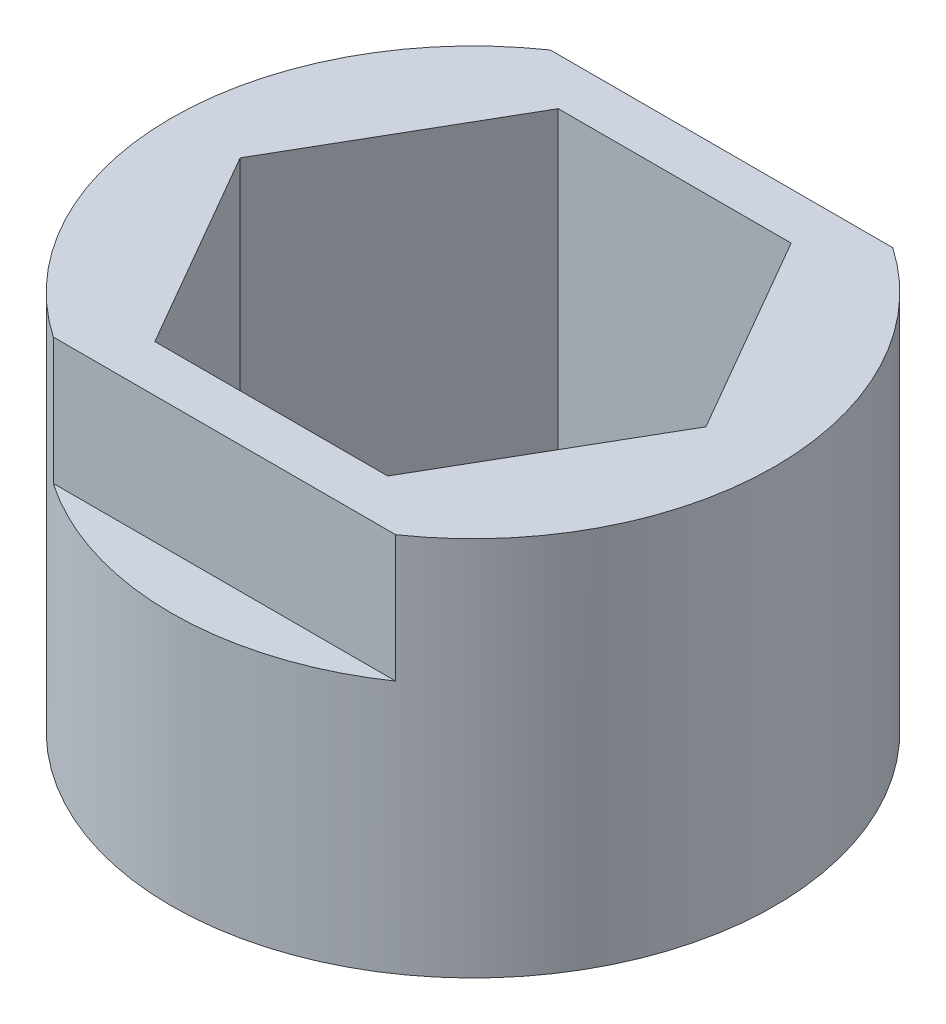
SolidWorks part; units mm, degrees
material "Polyester Resin"
ref_plane "Front Plane" through (0, 0, 0) normal (0, 0, 1) x (1, 0, 0)
ref_plane "Top Plane" through (0, 0, 0) normal (0, 1, 0) x (1, 0, 0)
ref_plane "Right Plane" through (0, 0, 0) normal (1, 0, 0) x (0, 0, -1)
sketch "Sketch1" plane through (0, 0, 0) normal (0, 1, 0) x (1, 0, 0)
  line L1 (-2.9156, 5.05) -> (-5.8312, 0)
  line L2 (-5.8312, 0) -> (-2.9156, -5.05)
  line L3 (-2.9156, -5.05) -> (2.9156, -5.05)
  line L4 (2.9156, -5.05) -> (5.8312, 0)
  line L5 (5.8312, 0) -> (2.9156, 5.05)
  line L6 (2.9156, 5.05) -> (-2.9156, 5.05)
  circle A0 centre (0, 0) radius 5.05 construction
  circle A1 centre (0, 0) radius 7.5565
  dimension "D2" = 15.113
  dimension "D1" = 10.1
extrude "Boss-Extrude1" add sketch "Sketch1" along normal blind 8.89
sketch "Sketch2" plane through (0, 0, 0) normal (0, -1, 0) x (1, 0, 0)
  circle A0 centre (0, 0) radius 7.5565
  circle A1 centre (0, 0) radius 3.3
  dimension "D1" = 6.6
extrude "Boss-Extrude2" add sketch "Sketch2" along normal blind 0.635
sketch "Sketch3" plane through (0, 0, 0) normal (1, 0, 0) x (0, 0, -1)
  line L0 (-6.223, 9.525) -> (-6.223, 5.715)
  line L1 (6.223, 9.525) -> (6.223, 5.715)
  line L2 (-7.5565, -0.635) -> (7.5565, -0.635) construction
  line L3 (-6.223, 9.525) -> (-8.202, 9.525)
  line L4 (-8.202, 9.525) -> (-8.202, 5.715)
  line L5 (-8.202, 5.715) -> (-6.223, 5.715)
  line L6 (6.223, 9.525) -> (8.4791, 9.525)
  line L7 (8.4791, 9.525) -> (8.4791, 5.715)
  line L8 (8.4791, 5.715) -> (6.223, 5.715)
  dimension "D1" = 12.446
  dimension "D2" = 6.223
  dimension "D3" = 3.81
  dimension "D4" = 3.81
  dimension "D5" = 6.35
  dimension "D6" = 6.35
extrude "Cut-Extrude1" cut sketch "Sketch3" against normal through all and the other way through all
equation "\"AB_Central_Bushing_Length\"= .75in"
equation "\"Solid_Length\"= .025in"
equation "\"Hex_Length\"= 0.35"
equation "\"D1@Boss-Extrude1\"= \"Hex_Length\""
equation "\"D1@Boss-Extrude2\"=\"Solid_Length\""
equation "\"Cutout_Angle\"= 80"
